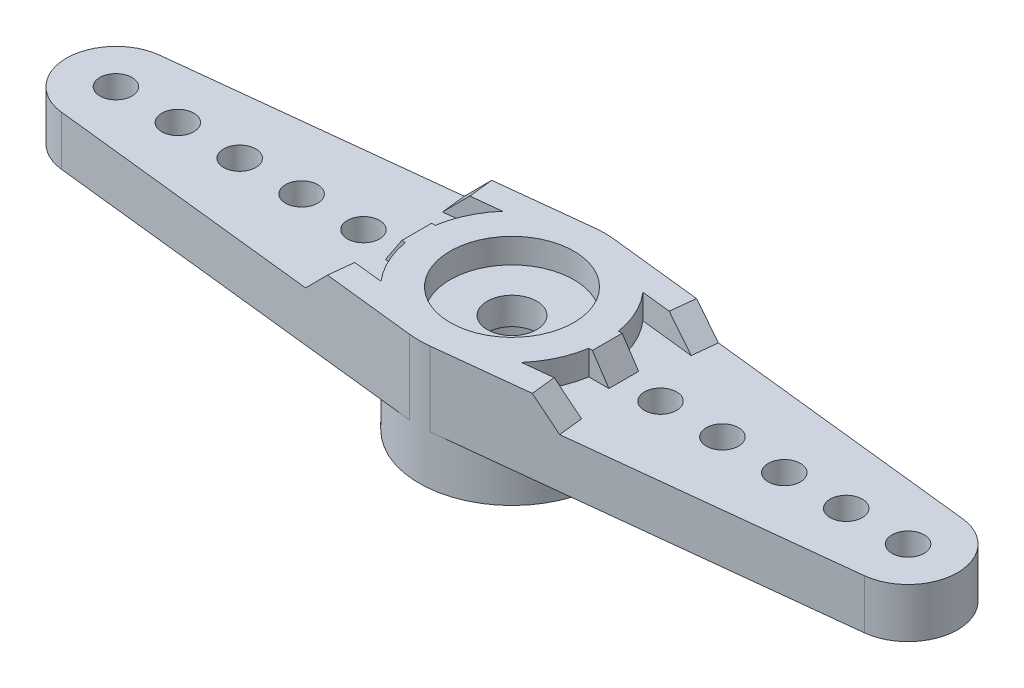
SolidWorks part; units mm, degrees
ref_plane "前视基准面" through (0, 0, 0) normal (0, 0, 1) x (1, 0, 0)
ref_plane "上视基准面" through (0, 0, 0) normal (0, 1, 0) x (1, 0, 0)
ref_plane "右视基准面" through (0, 0, 0) normal (1, 0, 0) x (0, 0, -1)
sketch "草图1" plane through (0, 0, 0) normal (0, 1, 0) x (1, 0, 0)
  line L0 (0.4102, 3.7275) -> (16.2188, 1.988)
  line L1 (0.4102, -3.7275) -> (16.2188, -1.988)
  arc A0 (0.4102, 3.7275) -> (0.4102, -3.7275) centre (0, 0) ccw
  arc A1 (16.2188, -1.988) -> (16.2188, 1.988) centre (16, 0) ccw
  circle A2 centre (16, 0) radius 0.65
  circle A3 centre (6, 0) radius 0.65
  circle A4 centre (8.5, 0) radius 0.65
  circle A5 centre (11, 0) radius 0.65
  circle A6 centre (13.5, 0) radius 0.65
  circle A7 centre (0, 0) radius 1
  dimension "D1" = 4
  dimension "D2" = 7.5
  dimension "D8" = 1.3
  dimension "D9" = 2
  dimension "D3" = 16
  dimension "D4" = 10
  dimension "D5" = 2.5
  dimension "D6" = 2.5
  dimension "D7" = 2.5
extrude "凸台-拉伸1" add sketch "草图1" along normal blind 2
sketch "草图2" plane through (0, 0, 0) normal (0, -1, 0) x (1, 0, 0)
  circle A0 centre (0, 0) radius 3.75
  circle A1 centre (0, 0) radius 1 construction
  circle A2 centre (0, 0) radius 1
extrude "凸台-拉伸2" add sketch "草图2" along normal blind 1.5
sketch "草图3" plane through (0, 2, 0) normal (0, 1, 0) x (1, 0, 0)
  circle A0 centre (0, 0) radius 3.75
  circle A1 centre (0, 0) radius 1 construction
  circle A2 centre (0, 0) radius 1
extrude "凸台-拉伸3" add sketch "草图3" along normal blind 1.5
sketch "草图4" plane through (0.4102, 0, 3.7275) normal (0.1094, 0, 0.994) x (0.994, 0, -0.1094)
  line L0 (0, 2) -> (0, 3.5)
  line L1 (1, 3.5) -> (-1, 3.5) construction
  line L2 (0, 3.5) -> (3.75, 3.5)
  line L3 (3.75, 3.5) -> (5.25, 2)
  line L4 (0, 2) -> (15.904, 2) construction
  line L5 (5.25, 2) -> (0, 2)
  dimension "D1" = 45
extrude "凸台-拉伸4" add sketch "草图4" against normal blind 1
mirror "镜向1" about plane through (0, 0, 0) normal (0, 0, 1) of "凸台-拉伸1", "凸台-拉伸4"
sketch "草图5" plane through (0, -1.5, 0) normal (0, -1, 0) x (1, 0, 0)
  circle A0 centre (0, 0) radius 2.5
  dimension "D1" = 5
extrude "切除-拉伸1" cut sketch "草图5" against normal blind 2.5
sketch "草图6" plane through (0, 3.5, 0) normal (0, 1, 0) x (1, 0, 0)
  circle A0 centre (0, 0) radius 2.5
  dimension "D1" = 5
extrude "切除-拉伸2" cut sketch "草图6" against normal blind 1.5
mirror "镜向2" about plane through (0, 0, 0) normal (1, 0, 0) of "镜向1", "凸台-拉伸4", "凸台-拉伸1"
sketch "草图7" plane through (0, 3.5, 0) normal (0, 1, 0) x (1, 0, 0)
  line L0 (0, 0) -> (0, -4.769) construction
  line L1 (2.6518, 0.6) -> (4.8482, 0.6)
  line L2 (2.6518, 0.6) -> (2.6518, -0.6)
  line L3 (2.6518, -0.6) -> (4.8482, -0.6)
  line L4 (4.8482, 0.6) -> (4.8482, -0.6)
  line L5 (2.6518, 0.6) -> (4.8482, -0.6) construction
  line L6 (2.6518, -0.6) -> (4.8482, 0.6) construction
  line L7 (-2.6518, -0.6) -> (-4.8482, 0.6) construction
  line L8 (-2.6518, 0.6) -> (-4.8482, -0.6) construction
  line L9 (-4.8482, 0.6) -> (-4.8482, -0.6)
  line L10 (-2.6518, -0.6) -> (-4.8482, -0.6)
  line L11 (-2.6518, 0.6) -> (-2.6518, -0.6)
  line L12 (-2.6518, 0.6) -> (-4.8482, 0.6)
  arc A0 (2.835, -2.4546) -> (2.835, 2.4546) centre (0, 0) ccw construction
  point P0 (3.75, 0)
  point P15 (-3.75, 0)
  dimension "D1" = 1.2
extrude "凸台-拉伸5" add sketch "草图7" against normal up to surface (1.5 mm away) up to face at (-7.8875, 2, 0)
chamfer "倒角1" distance 1.5 distance2 1 2 edges at (4.8482, 3.5, 0) (-4.8482, 3.5, 0) first distance on face at (4.8482, 2.75, 0) first distance on face at (-4.8482, 2.75, 0)
sketch "草图8" plane through (0, 2, 0) normal (0, 1, 0) x (1, 0, 0)
  line L0 (-5.6287, -3.1533) -> (-16.2188, -1.988) construction
  line L1 (-5.6287, -3.1533) -> (-4.1377, -3.3173) construction
  line L2 (-4.1377, -3.3173) -> (-0.4102, -3.7275) construction
  line L3 (4.1377, -3.3173) -> (0.4102, -3.7275) construction
  line L4 (5.6287, -3.1533) -> (4.1377, -3.3173) construction
  line L5 (5.6287, -3.1533) -> (16.2188, -1.988) construction
  line L6 (16.2188, 1.988) -> (5.6287, 3.1533) construction
  line L7 (5.6287, 3.1533) -> (4.1377, 3.3173) construction
  line L8 (4.1377, 3.3173) -> (0.4102, 3.7275) construction
  line L9 (-4.1377, 3.3173) -> (-0.4102, 3.7275) construction
  line L10 (-5.6287, 3.1533) -> (-4.1377, 3.3173) construction
  line L11 (-16.2188, 1.988) -> (-5.6287, 3.1533) construction
  line L12 (-5.6287, -3.1533) -> (-16.2188, -1.988)
  line L13 (-5.6287, -3.1533) -> (-4.1377, -3.3173)
  line L14 (-4.1377, -3.3173) -> (-0.4102, -3.7275)
  line L15 (4.1377, -3.3173) -> (0.4102, -3.7275)
  line L16 (5.6287, -3.1533) -> (4.1377, -3.3173)
  line L17 (5.6287, -3.1533) -> (16.2188, -1.988)
  line L18 (16.2188, 1.988) -> (5.6287, 3.1533)
  line L19 (5.6287, 3.1533) -> (4.1377, 3.3173)
  line L20 (4.1377, 3.3173) -> (0.4102, 3.7275)
  line L21 (-4.1377, 3.3173) -> (-0.4102, 3.7275)
  line L22 (-5.6287, 3.1533) -> (-4.1377, 3.3173)
  line L23 (-16.2188, 1.988) -> (-5.6287, 3.1533)
  circle A0 centre (0, 0) radius 1 construction
  circle A1 centre (16, 0) radius 0.65 construction
  circle A2 centre (13.5, 0) radius 0.65 construction
  circle A3 centre (11, 0) radius 0.65 construction
  circle A4 centre (8.5, 0) radius 0.65 construction
  circle A5 centre (6, 0) radius 0.65 construction
  circle A6 centre (-6, 0) radius 0.65 construction
  circle A7 centre (-8.5, 0) radius 0.65 construction
  circle A8 centre (-11, 0) radius 0.65 construction
  circle A9 centre (-13.5, 0) radius 0.65 construction
  circle A10 centre (-16, 0) radius 0.65 construction
  arc A11 (-16.2188, 1.988) -> (-16.2188, -1.988) centre (-16, 0) ccw construction
  arc A12 (-0.4102, -3.7275) -> (0.4102, -3.7275) centre (0, 0) ccw construction
  arc A13 (16.2188, -1.988) -> (16.2188, 1.988) centre (16, 0) ccw construction
  circle A14 centre (0, 0) radius 1
  circle A15 centre (16, 0) radius 0.65
  circle A16 centre (13.5, 0) radius 0.65
  circle A17 centre (11, 0) radius 0.65
  circle A18 centre (8.5, 0) radius 0.65
  circle A19 centre (6, 0) radius 0.65
  circle A20 centre (-6, 0) radius 0.65
  circle A21 centre (-8.5, 0) radius 0.65
  circle A22 centre (-11, 0) radius 0.65
  circle A23 centre (-13.5, 0) radius 0.65
  circle A24 centre (-16, 0) radius 0.65
  arc A25 (-16.2188, 1.988) -> (-16.2188, -1.988) centre (-16, 0) ccw
  arc A26 (-0.4102, -3.7275) -> (0.4102, -3.7275) centre (0, 0) ccw
  arc A27 (16.2188, -1.988) -> (16.2188, 1.988) centre (16, 0) ccw
  arc A28 (0.4102, 3.7275) -> (-0.4102, 3.7275) centre (0, 0) ccw construction
  arc A29 (0.4102, 3.7275) -> (-0.4102, 3.7275) centre (0, 0) ccw
extrude "凸台-拉伸6" add sketch "草图8" along normal blind 0.5
sketch "草图9" plane through (0, 0, 0) normal (0, -1, 0) x (1, 0, 0)
  line L0 (0.4102, -3.7275) -> (16.2188, -1.988) construction
  line L1 (16.2188, 1.988) -> (0.4102, 3.7275) construction
  line L2 (-16.2188, -1.988) -> (-0.4102, -3.7275) construction
  line L3 (-0.4102, 3.7275) -> (-16.2188, 1.988) construction
  line L4 (0.4102, -3.7275) -> (16.2188, -1.988)
  line L5 (16.2188, 1.988) -> (0.4102, 3.7275)
  line L6 (-16.2188, -1.988) -> (-0.4102, -3.7275)
  line L7 (-0.4102, 3.7275) -> (-16.2188, 1.988)
  arc A0 (0.4102, -3.7275) -> (0.4102, 3.7275) centre (0, 0) ccw construction
  arc A1 (16.2188, -1.988) -> (16.2188, 1.988) centre (16, 0) ccw construction
  arc A2 (-0.4102, 3.7275) -> (-0.4102, -3.7275) centre (0, 0) ccw construction
  arc A3 (-16.2188, 1.988) -> (-16.2188, -1.988) centre (-16, 0) ccw construction
  arc A4 (0.4102, -3.7275) -> (0.4102, 3.7275) centre (0, 0) ccw
  arc A5 (16.2188, -1.988) -> (16.2188, 1.988) centre (16, 0) ccw
  arc A6 (-0.4102, 3.7275) -> (-0.4102, -3.7275) centre (0, 0) ccw
  arc A7 (-16.2188, 1.988) -> (-16.2188, -1.988) centre (-16, 0) ccw
extrude "切除-拉伸3" cut sketch "草图9" against normal blind 0.5
sketch "草图10" plane through (0, 0, 0) normal (0, -1, 0) x (1, 0, 0)
  circle A1 centre (0, 0) radius 2.5
  circle A2 centre (0, 0) radius 2.5
  dimension "D1" = 0
extrude "切除-拉伸4" cut sketch "草图10" against normal blind 1.4
sketch "草图11" plane through (0, -1.5, 0) normal (0, -1, 0) x (1, 0, 0)
  circle A0 centre (0, 0) radius 2.65
  dimension "D1" = 5.3
extrude "切除-拉伸5" cut sketch "草图11" against normal up to surface (2.9 mm away) up to face at (0, 1.4, -1)
